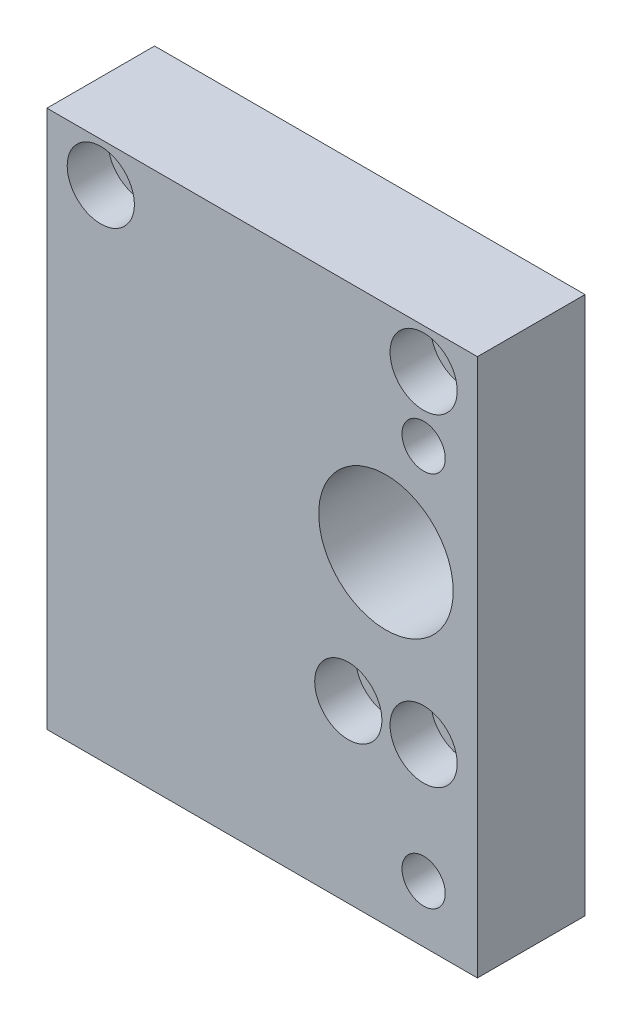
SolidWorks part; units mm, degrees
material "1060 Alloy"
ref_plane "Front Plane" through (0, 0, 0) normal (0, 0, 1) x (1, 0, 0)
ref_plane "Top Plane" through (0, 0, 0) normal (0, 1, 0) x (1, 0, 0)
ref_plane "Right Plane" through (0, 0, 0) normal (1, 0, 0) x (0, 0, -1)
sketch "Sketch1" plane through (0, 0, 0) normal (0, 0, 1) x (1, 0, 0)
  line L0 (0, 25.4) -> (0, -25.4) construction
  line L1 (-25.4, -25.4) -> (25.4, -25.4)
  line L2 (-25.4, -25.4) -> (-25.4, 25.4)
  line L3 (-25.4, 25.4) -> (25.4, 25.4)
  line L4 (25.4, -25.4) -> (25.4, 25.4)
  line L5 (-25.4, -25.4) -> (25.4, 25.4) construction
  line L6 (-25.4, 25.4) -> (25.4, -25.4) construction
  line L7 (25.4, 0) -> (-25.4, 0) construction
  circle A0 centre (-19.05, 20.701) radius 2.5527
  circle A1 centre (19.05, 20.701) radius 2.5527
  circle A2 centre (19.05, -17.399) radius 2.5527
  circle A3 centre (10.16, -17.399) radius 2.5527
  circle A4 centre (14.605, 0) radius 7.9375
  point P0 (0, 0)
  dimension "D3" = 5.1054
  dimension "D7" = 15.875
  dimension "D1" = 50.8
  dimension "D2" = 50.8
  dimension "D4" = 19.05
  dimension "D5" = 20.701
  dimension "D6" = 4.445
  dimension "D8" = 38.1
  dimension "D9" = 8.89
extrude "Boss-Extrude1" add sketch "Sketch1" along normal blind 12.7
sketch "Sketch2" plane through (0, -25.4, 0) normal (0, -1, 0) x (1, 0, 0)
  line L1 (-25.4, 0) -> (25.4, 0)
  line L2 (-25.4, 0) -> (-25.4, 12.7)
  line L3 (-25.4, 12.7) -> (25.4, 12.7)
  line L4 (25.4, 0) -> (25.4, 12.7)
extrude "Boss-Extrude2" add sketch "Sketch2" along normal blind 12.7
hole_wizard "CBORE for #10 Socket Head Cap Screw1" positions "Sketch4" profile "Sketch5" counterbore size "#10" standard "ANSI Inch" end condition through all
sketch "Sketch4" plane through (-24.7212, -12.8643, 0) normal (0, 0, 1) x (1, 0, 0)
  line L0 (50.1212, -25.2357) -> (50.1212, 38.2643) construction
  circle A0 centre (43.7712, 33.5653) radius 2.5527 construction
  point P0 (43.7712, -18.5047)
  point P7 (43.7712, 25.9453)
  dimension "D3" = 7.62
  dimension "D1" = 6.35
  dimension "D2" = 44.45
sketch "Sketch5" plane through (19.05, -31.369, 0) normal (1, 0, 0) x (0, 1, 0)
  line L0 (0, 0) -> (0, 12.7)
  line L1 (0, 12.7) -> (2.5527, 12.7)
  line L3 (2.5527, 12.7) -> (2.5527, 4.826)
  line L4 (2.5527, 4.826) -> (3.9624, 4.826)
  line L5 (3.9624, 4.826) -> (3.9624, 0)
  line L7 (3.9624, 0) -> (0, 0)
  line L11 (0, -6.35) -> (0, 107.95) construction
  dimension "Thru Hole Dia." = 5.1054
  dimension "Thru Hole Depth" = 12.7
  dimension "C'Bore Dia." = 7.9248
  dimension "C'Bore Depth" = 4.826
sketch "Sketch6" plane through (0, 0, 12.7) normal (0, 0, -1) x (-1, 0, 0)
  circle A0 centre (-19.05, 20.701) radius 3.9624
  circle A3 centre (-19.05, -17.399) radius 3.9624
  circle A4 centre (-10.16, -17.399) radius 3.9624
  circle A5 centre (19.05, 20.701) radius 3.9624
  dimension "D1" = 7.9248
extrude "Cut-Extrude1" cut sketch "Sketch6" along normal blind 4.826
